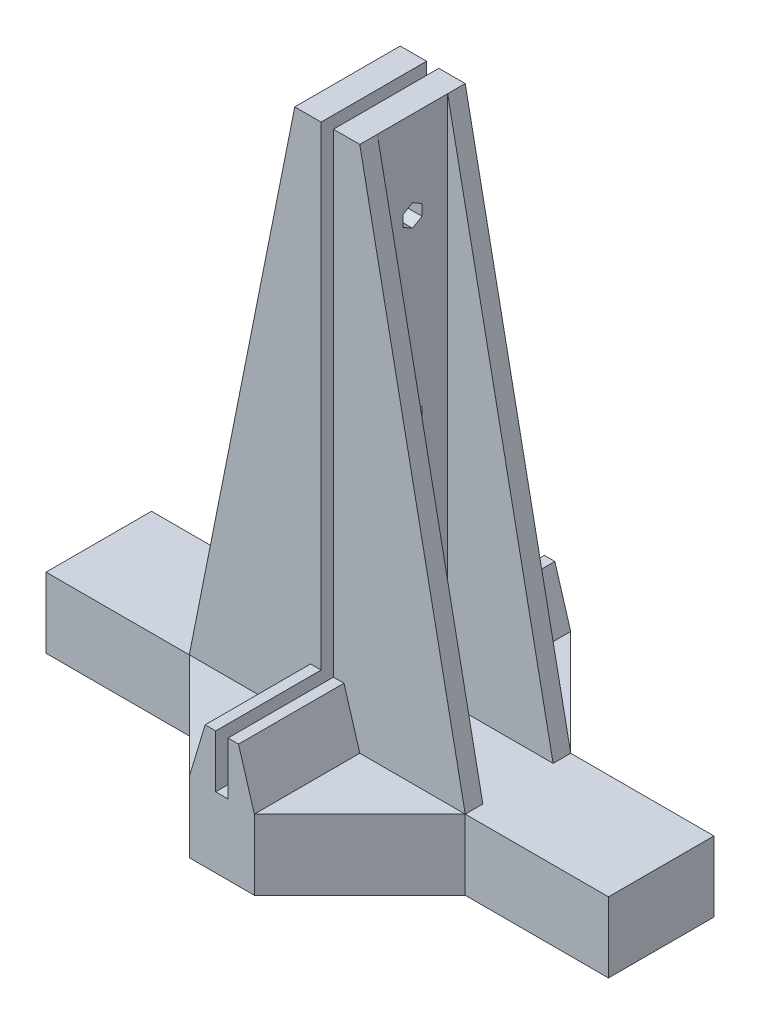
SolidWorks part; units mm, degrees
ref_plane "Front Plane" through (0, 0, 0) normal (0, 0, 1) x (1, 0, 0)
ref_plane "Top Plane" through (0, 0, 0) normal (0, 1, 0) x (1, 0, 0)
ref_plane "Right Plane" through (0, 0, 0) normal (1, 0, 0) x (0, 0, -1)
sketch "Sketch1" plane through (0, 0, 0) normal (0, 0, 1) x (1, 0, 0)
  line L0 (0, 0) -> (80, 0)
  line L1 (55, 0) -> (-55, 0) construction
  line L2 (80, 0) -> (80, 20)
  line L3 (80, 20) -> (9.25, 20)
  line L4 (9.25, 20) -> (9.25, 170)
  line L5 (9.25, 170) -> (1.75, 170)
  line L6 (1.75, 170) -> (1.75, 20)
  line L7 (1.75, 20) -> (-1.75, 20)
  line L8 (-1.75, 20) -> (-1.75, 170)
  line L9 (-1.75, 170) -> (-9.25, 170)
  line L10 (-9.25, 170) -> (-9.25, 20)
  line L11 (-9.25, 20) -> (-80, 20)
  line L12 (-80, 20) -> (-80, 0)
  line L13 (-80, 0) -> (0, 0)
  point P15 (0, 20)
  dimension "D1" = 80
  dimension "D2" = 20
  dimension "D4" = 150
  dimension "D5" = 7.5
  dimension "D6" = 3.5
  dimension "D7" = 160
  dimension "D8" = 7.5
extrude "Boss-Extrude3" add sketch "Sketch1" along normal blind 30
sketch "Sketch3" plane through (9.25, 0, 0) normal (1, 0, 0) x (0, 0, -1)
  line L0 (-30, 170) -> (0, 170) construction
  line L3 (-30, 20) -> (0, 20) construction
  circle A0 centre (-15, 95) radius 1.8
  circle A1 centre (-15, 45) radius 1.8
  circle A2 centre (-15, 145) radius 1.8
  point P0 (-15, 170)
  point P11 (0, 0)
  point P12 (-12.9998, 135.7755)
  dimension "D3" = 3.6
  dimension "D2" = 3.6
  dimension "D4" = 25
  dimension "D5" = 50
  dimension "D1" = 50
extrude "Cut-Extrude1" cut sketch "Sketch3" against normal blind 161 and the other way blind 88
sketch "Sketch4" plane through (0, 0, 0) normal (0, 0, 1) x (1, 0, 0)
  line L0 (9.25, 170) -> (39.25, 20)
  line L1 (80, 20) -> (9.25, 20) construction
  line L2 (39.25, 20) -> (9.25, 20)
  line L3 (9.25, 20) -> (9.25, 170)
  line L4 (0, -1000) -> (0, 49000) construction
  line L6 (-9.25, 20) -> (-9.25, 170)
  line L7 (-39.25, 20) -> (-9.25, 20)
  line L8 (-9.25, 170) -> (-39.25, 20)
  dimension "D1" = 30
extrude "Boss-Extrude4" add sketch "Sketch4" along normal blind 5
extrude "Boss-Extrude5" add sketch "Sketch4<2>" against normal blind 5 from surface starting at face at (0, 66.6667, 30)
sketch "Sketch4<2>" plane through (0, 0, 0) normal (0, 0, 1) x (1, 0, 0) same geometry as "Sketch4"
sketch "Sketch5" plane through (0, 20, 0) normal (0, 1, 0) x (1, 0, 0)
  line L0 (9.25, -25) -> (9.25, -5) construction
  line L1 (-9.25, 30) -> (9.25, 30)
  line L2 (-9.25, 30) -> (-9.25, -60) construction
  line L3 (-9.25, -60) -> (9.25, -60)
  line L4 (9.25, 30) -> (9.25, -60) construction
  line L5 (-9.25, 30) -> (9.25, -60) construction
  line L6 (-9.25, -60) -> (9.25, 30) construction
  line L7 (-9.25, -25) -> (-9.25, -5) construction
  line L8 (39.25, 0) -> (9.25, 0) construction
  line L9 (-39.25, 0) -> (-9.25, 30)
  line L10 (-39.25, 0) -> (-9.25, 0)
  line L12 (39.25, 0) -> (9.25, 30)
  line L13 (-39.25, -30) -> (-9.25, -30)
  line L14 (-39.25, -30) -> (-9.25, -60)
  line L15 (-9.25, 0) -> (-9.25, -30)
  line L16 (9.25, -60) -> (39.25, -30)
  line L17 (39.25, -30) -> (39.25, 0)
  point P0 (0, -15)
  point P5 (9.25, -15)
  dimension "D1" = 30
extrude "Boss-Extrude6" add sketch "Sketch5" against normal up to surface (20 mm away) up to face at (0, 0, 15)
sketch "Sketch7" plane through (0, 0, 30) normal (0, 0, 1) x (1, 0, 0)
  line L0 (0, -1000) -> (0, 49000) construction
  line L1 (9.25, 0) -> (-9.25, 0) construction
  line L2 (-1.75, 35) -> (-1.75, 20)
  line L3 (-1.75, 20) -> (-1.75, 170) construction
  line L4 (-1.75, 20) -> (-9.25, 20)
  line L7 (1.75, 20) -> (9.25, 20)
  line L8 (1.75, 35) -> (1.75, 20)
  line L9 (-1.75, 35) -> (-4.75, 35)
  line L10 (-4.75, 35) -> (-9.25, 20)
  line L11 (4.75, 35) -> (9.25, 20)
  line L12 (1.75, 35) -> (4.75, 35)
  point P5 (0, 0)
  dimension "D1" = 15
  dimension "D2" = 3
extrude "Boss-Extrude7" add sketch "Sketch7" along normal up to surface (30 mm away) up to face at (0, 10, 60)
extrude "Boss-Extrude8" add sketch "Sketch7<2>" along direction (0, 0, -1) on the side against the normal up to surface (60 mm away) from surface up to face at (0, 10, -30) starting at face at (59.625, 10, 0)
sketch "Sketch7<2>" plane through (0, 0, 30) normal (0, 0, 1) x (1, 0, 0) same geometry as "Sketch7"
sketch "Sketch8" plane through (9.25, 0, 0) normal (1, 0, 0) x (0, 0, -1)
  line L1 (-15, 91.8534) -> (-12.275, 93.4267)
  line L2 (-12.275, 93.4267) -> (-12.275, 96.5733)
  line L3 (-12.275, 96.5733) -> (-15, 98.1466)
  line L4 (-15, 98.1466) -> (-17.725, 96.5733)
  line L5 (-17.725, 96.5733) -> (-17.725, 93.4267)
  line L6 (-17.725, 93.4267) -> (-15, 91.8534)
  line L7 (-15, 41.8534) -> (-12.275, 43.4267)
  line L8 (-12.275, 43.4267) -> (-12.275, 46.5733)
  line L9 (-12.275, 46.5733) -> (-15, 48.1466)
  line L10 (-15, 48.1466) -> (-17.725, 46.5733)
  line L11 (-17.725, 46.5733) -> (-17.725, 43.4267)
  line L12 (-17.725, 43.4267) -> (-15, 41.8534)
  line L13 (-15, 141.8534) -> (-12.275, 143.4267)
  line L14 (-12.275, 143.4267) -> (-12.275, 146.5733)
  line L15 (-12.275, 146.5733) -> (-15, 148.1466)
  line L16 (-15, 148.1466) -> (-17.725, 146.5733)
  line L17 (-17.725, 146.5733) -> (-17.725, 143.4267)
  line L18 (-17.725, 143.4267) -> (-15, 141.8534)
  circle A0 centre (-15, 95) radius 2.725 construction
  circle A1 centre (-15, 45) radius 2.725 construction
  circle A2 centre (-15, 145) radius 2.725 construction
  dimension "D1" = 5.45
extrude "Cut-Extrude2" cut sketch "Sketch8" against normal blind 4
